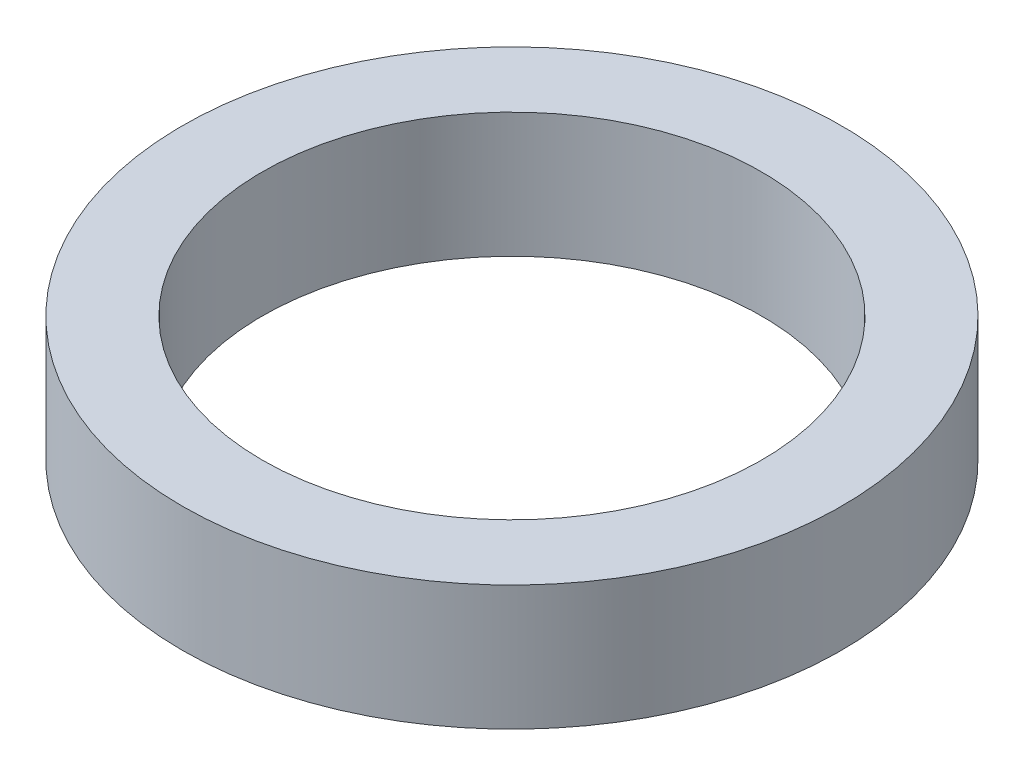
SolidWorks part; units mm, degrees
material "6061-T6 (SS)"
ref_plane "Front Plane" through (0, 0, 0) normal (0, 0, 1) x (1, 0, 0)
ref_plane "Top Plane" through (0, 0, 0) normal (0, 1, 0) x (1, 0, 0)
ref_plane "Right Plane" through (0, 0, 0) normal (1, 0, 0) x (0, 0, -1)
sketch "Sketch1" plane through (0, 0, 0) normal (0, 1, 0) x (1, 0, 0)
  circle A0 centre (0, 0) radius 3.175
  circle A1 centre (0, 0) radius 4.191
  dimension "D1" = 6.35
  dimension "D2" = 1.016
extrude "Boss-Extrude1" add sketch "Sketch1" along normal blind 1.5875
